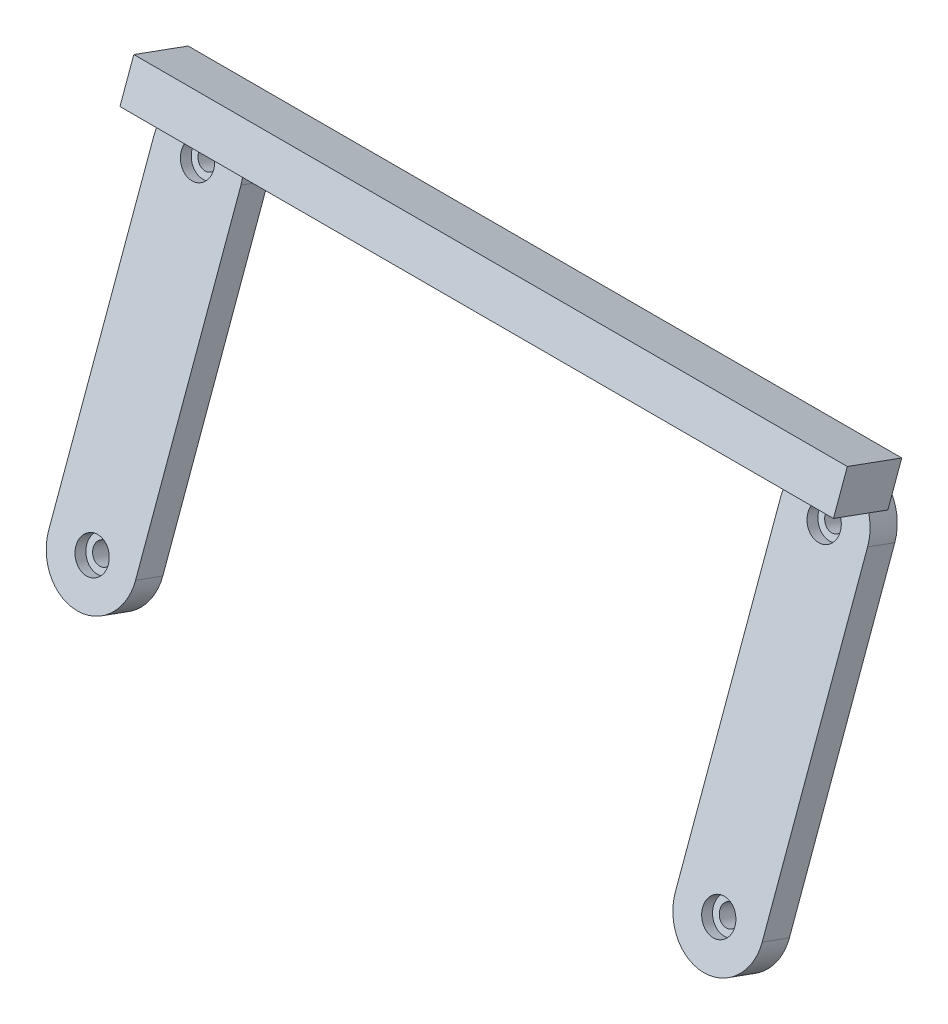
SolidWorks part; units mm, degrees
ref_plane "Plan de face" through (0, 0, 0) normal (0, 0, 1) x (1, 0, 0)
ref_plane "Plan de dessus" through (0, 0, 0) normal (0, 1, 0) x (1, 0, 0)
ref_plane "Plan de droite" through (0, 0, 0) normal (1, 0, 0) x (0, 0, -1)
ref_axis "Axe1" through (-88.99, 0, 0) along (1, 0, 0)
ref_plane "Plan1" through (0, 0, 0) normal (0, 0.342, 0.9397) x (1, 0, 0)
sketch "Esquisse3" plane through (0, 0, 0) normal (0, 0.342, 0.9397) x (1, 0, 0)
  line L1 (-54.1, 26.6) -> (54.1, 26.6) construction
  line L2 (-54.1, 26.6) -> (-54.1, -26.6) construction
  line L3 (-54.1, -26.6) -> (54.1, -26.6) construction
  line L4 (54.1, 26.6) -> (54.1, -26.6) construction
  line L5 (-54.1, 26.6) -> (54.1, -26.6) construction
  line L6 (-54.1, -26.6) -> (54.1, 26.6) construction
  circle A0 centre (-54.1, 26.6) radius 2.8
  circle A1 centre (54.1, 26.6) radius 2.8
  circle A2 centre (54.1, -26.6) radius 2.8
  circle A3 centre (-54.1, -26.6) radius 2.8
  circle A4 centre (-54.1, 26.6) radius 7.5
  circle A5 centre (54.1, 26.6) radius 7.5
  circle A6 centre (54.1, -26.6) radius 7.5
  circle A7 centre (-54.1, -26.6) radius 7.5
  point P0 (0, 0)
  dimension "D3" = 5.6
  dimension "D4" = 15
  dimension "D1" = 53.2
  dimension "D2" = 108.2
extrude "Boss.-Extru.1" add sketch "Esquisse3" along normal blind 2
sketch "Esquisse4" plane through (0, 0, 0) normal (0, -0.342, -0.9397) x (-1, 0, 0)
  circle A0 centre (-54.1, 26.6) radius 1.7
  circle A1 centre (-54.1, 26.6) radius 7.5
  circle A2 centre (54.1, 26.6) radius 1.7
  circle A3 centre (54.1, 26.6) radius 7.5
  circle A4 centre (54.1, -26.6) radius 1.7
  circle A5 centre (54.1, -26.6) radius 7.5
  circle A6 centre (-54.1, -26.6) radius 1.7
  circle A7 centre (-54.1, -26.6) radius 7.5
  circle A8 centre (-54.1, 26.6) radius 7.5 construction
  point P16 (0, 0)
  dimension "D1" = 3.4
extrude "Boss.-Extru.2" add sketch "Esquisse4" along normal blind 3
sketch "Esquisse5" plane through (0, -1.0261, -2.8191) normal (0, -0.342, -0.9397) x (-1, 0, 0)
  line L0 (-61.6, 26.6) -> (-61.6, -26.6)
  line L1 (-46.6, -26.6) -> (-46.6, 26.6)
  line L2 (-61.6, -26.6) -> (-46.6, -26.6) construction
  line L3 (-61.6, 26.6) -> (-46.6, 26.6) construction
  line L4 (0, 0) -> (0, 28.7857) construction
  line L5 (61.6, 26.6) -> (61.6, -26.6)
  line L6 (46.6, -26.6) -> (46.6, 26.6)
  circle A0 centre (-54.1, 26.6) radius 7.5 construction
  circle A1 centre (-54.1, -26.6) radius 7.5 construction
  arc A2 (-61.6, 26.6) -> (-46.6, 26.6) centre (-54.1, 26.6) ccw
  arc A3 (-61.6, -26.6) -> (-46.6, -26.6) centre (-54.1, -26.6) cw
  arc A4 (61.6, 26.6) -> (46.6, 26.6) centre (54.1, 26.6) cw
  arc A5 (61.6, -26.6) -> (46.6, -26.6) centre (54.1, -26.6) ccw
extrude "Boss.-Extru.3" add sketch "Esquisse5" against normal up to surface (5 mm away) up to face at (54.1, 18.6322, -4.6532)
sketch "Esquisse6" plane through (0, 0.684, 1.8794) normal (0, 0.342, 0.9397) x (1, 0, 0)
  line L0 (-61.6, -26.6) -> (-61.6, 26.6) construction
  line L1 (-61.6, 38.35) -> (61.6, 38.35)
  line L2 (-61.6, 38.35) -> (-61.6, 31.35)
  line L3 (-61.6, 31.35) -> (61.6, 31.35)
  line L4 (61.6, 38.35) -> (61.6, 31.35)
  line L5 (61.6, 26.6) -> (61.6, -26.6) construction
  circle A0 centre (-54.1, 26.6) radius 1.7 construction
  dimension "D1" = 4.75
  dimension "D2" = 7
extrude "Boss.-Extru.4" add sketch "Esquisse6" along normal blind 10 from surface starting at face at (54.1, 26.5933, -9.6792)
